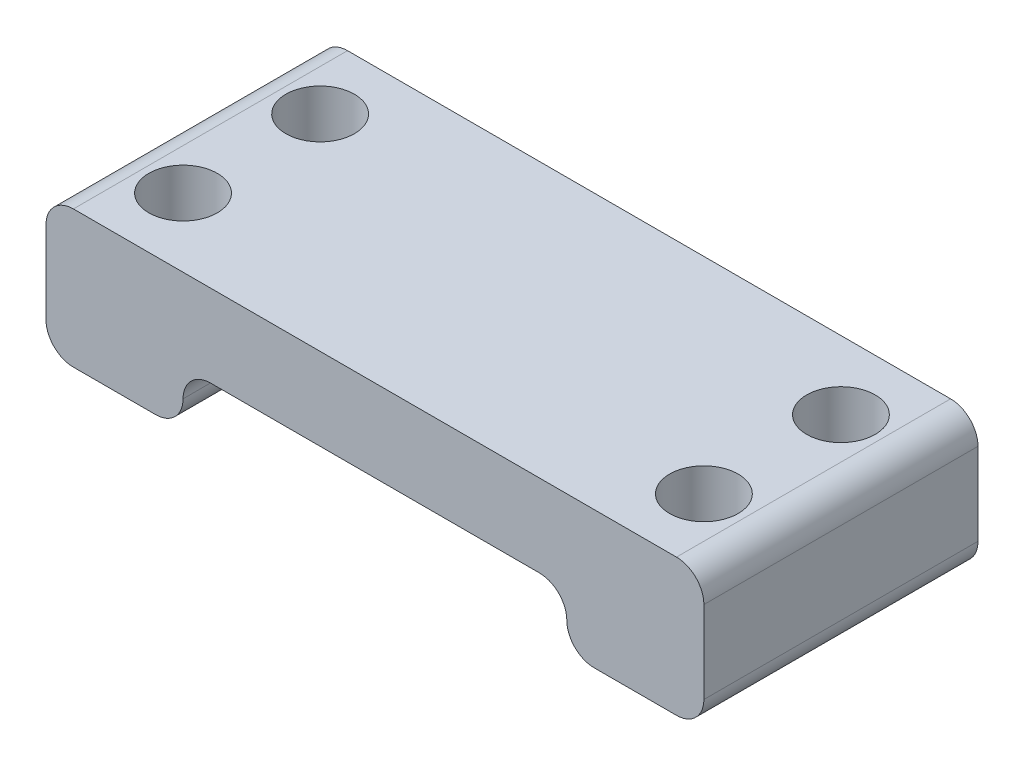
SolidWorks part; units mm, degrees
ref_plane "Front Plane" through (0, 0, 0) normal (0, 0, 1) x (1, 0, 0)
ref_plane "Top Plane" through (0, 0, 0) normal (0, 1, 0) x (1, 0, 0)
ref_plane "Right Plane" through (0, 0, 0) normal (1, 0, 0) x (0, 0, -1)
sketch "Sketch1" plane through (0, 0, 0) normal (0, 1, 0) x (1, 0, 0)
  line L1 (-12, 5) -> (12, 5)
  line L2 (-12, 5) -> (-12, -5)
  line L3 (-12, -5) -> (12, -5)
  line L4 (12, 5) -> (12, -5)
  line L5 (-12, 5) -> (12, -5) construction
  line L6 (-12, -5) -> (12, 5) construction
  point P0 (0, 0)
  dimension "D1" = 24
  dimension "D2" = 10
extrude "Boss-Extrude1" add sketch "Sketch1" along normal blind 5
sketch "Sketch2" plane through (0, 0, 5) normal (0, 0, 1) x (1, 0, 0)
  line L3 (-7, 2) -> (7, 2)
  line L4 (-7, 2) -> (-7, 0)
  line L5 (-7, 0) -> (7, 0)
  line L6 (7, 2) -> (7, 0)
  line L7 (-7, 2) -> (7, 0) construction
  line L8 (-7, 0) -> (7, 2) construction
  point P0 (0, 1)
  dimension "D1" = 2
  dimension "D2" = 14
extrude "Cut-Extrude1" cut sketch "Sketch2" against normal through all
fillet "Fillet1" radius 1 8 edges at (-12, 0, 0) (-12, 5, 0) (12, 5, 0) (12, 0, 0) (7, 0, 0) (7, 2, 0) (-7, 2, 0) (-7, 0, 0)
sketch "Sketch3" plane through (0, 5, 0) normal (0, 1, 0) x (1, 0, 0)
  line L0 (-11, -5) -> (-8, -5) construction
  line L1 (8, -5) -> (11, -5) construction
  line L3 (-20.5583, 0) -> (16.8021, 0) construction
  circle A0 centre (-9.5, 2.5) radius 1.25
  circle A1 centre (9.5, 2.5) radius 1.25
  circle A2 centre (-9.5, -2.5) radius 1.25
  circle A3 centre (9.5, -2.5) radius 1.25
  point P10 (0, 0)
  point P14 (-9.5, -5)
  point P18 (9.5, -5)
  dimension "D1" = 2.5
  dimension "D2" = 5
  dimension "D3" = 2.5
extrude "Cut-Extrude2" cut sketch "Sketch3" against normal through all
